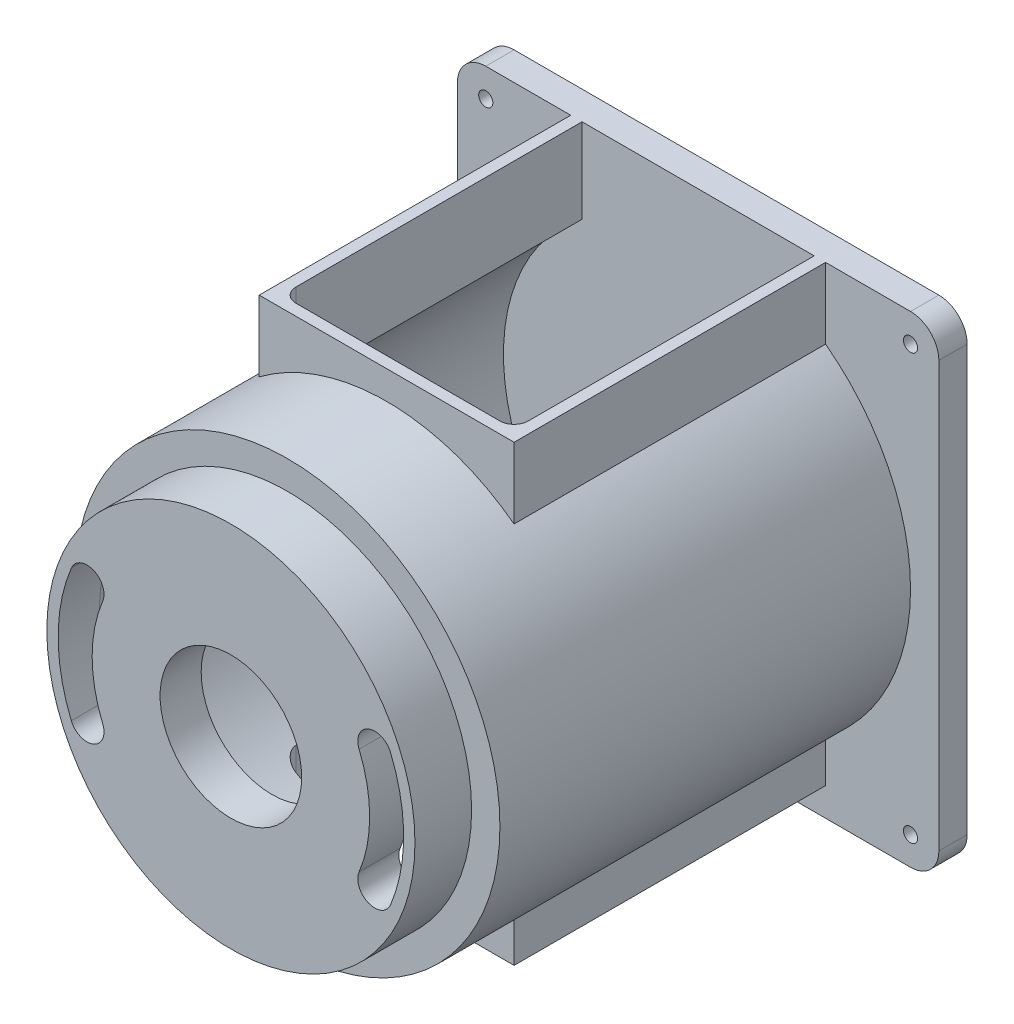
SolidWorks part; units mm, degrees
material "Cast Stainless Steel"
ref_plane "Front Plane" through (0, 0, 0) normal (0, 0, 1) x (1, 0, 0)
ref_plane "Top Plane" through (0, 0, 0) normal (0, 1, 0) x (1, 0, 0)
ref_plane "Right Plane" through (0, 0, 0) normal (1, 0, 0) x (0, 0, -1)
other "Center of Mass"
sketch "Sketch1" plane through (0, 0, 0) normal (0, 1, 0) x (1, 0, 0)
  line L1 (150, -170) -> (-150, -170)
  line L2 (170, -150) -> (170, 150)
  line L3 (150, 170) -> (-150, 170)
  line L4 (-170, -150) -> (-170, 150)
  line L5 (170, -170) -> (-170, 170) construction
  line L6 (170, 170) -> (-170, -170) construction
  arc A0 (170, -150) -> (150, -170) centre (150, -150) cw
  arc A1 (-170, -150) -> (-150, -170) centre (-150, -150) ccw
  arc A2 (150, 170) -> (170, 150) centre (150, 150) cw
  arc A3 (-150, 170) -> (-170, 150) centre (-150, 150) ccw
  point P0 (0, 0)
  dimension "D3" = 20
  dimension "D1" = 340
  dimension "D2" = 340
extrude "Boss-Extrude1" add sketch "Sketch1" along normal blind 20
sketch "Sketch2" plane through (0, 20, 0) normal (0, 1, 0) x (1, 0, 0)
  line L4 (170, -150) -> (170, 150)
  line L5 (150, 170) -> (-150, 170)
  line L6 (-170, 150) -> (-170, -150)
  line L7 (-150, -170) -> (150, -170)
  line L8 (170, -150) -> (170, 150)
  line L9 (150, 170) -> (-150, 170)
  line L10 (-170, 150) -> (-170, -150)
  line L11 (-150, -170) -> (150, -170)
  line L12 (-150, 0) -> (-150, -90)
  line L13 (-150, -90) -> (-120, -90)
  line L14 (120, -90) -> (150, -90)
  line L15 (0, 0) -> (-150, 0) construction
  line L16 (150, -150) -> (150, 150)
  line L17 (150, 150) -> (-150, 150)
  line L18 (-150, 150) -> (-150, -150)
  line L19 (-150, -150) -> (150, -150)
  line L20 (150, -150) -> (150, 150)
  line L21 (150, 150) -> (-150, 150)
  line L22 (-150, 150) -> (-150, -150)
  line L23 (-150, -150) -> (150, -150)
  line L24 (150, -90) -> (170, -90)
  line L25 (150, 90) -> (170, 90)
  line L26 (120, 90) -> (150, 90)
  line L27 (-150, 90) -> (-120, 90)
  arc A4 (150, -170) -> (170, -150) centre (150, -150) ccw
  arc A5 (170, 150) -> (150, 170) centre (150, 150) ccw
  arc A6 (-150, 170) -> (-170, 150) centre (-150, 150) ccw
  arc A7 (-170, -150) -> (-150, -170) centre (-150, -150) ccw
  arc A8 (150, -170) -> (170, -150) centre (150, -150) ccw
  arc A9 (170, 150) -> (150, 170) centre (150, 150) ccw
  arc A10 (-150, 170) -> (-170, 150) centre (-150, 150) ccw
  arc A11 (-170, -150) -> (-150, -170) centre (-150, -150) ccw
  circle A12 centre (0, 0) radius 150
  dimension "D3" = 30
  dimension "D1" = 0
  dimension "D2" = 20
extrude "Boss-Extrude2" add sketch "Sketch2" along normal blind 220 contours A12 | A12 L12 L13 | A12 L14 L20 | L25 L20 L24 L8 | A12 L20 L26 | A12 L27 L22 region at (160, 20, 0) region at (141.1785, 20, 67.9748) region at (141.1785, 20, -67.9748) region at (0, 20, 0) region at (-141.1785, 20, 67.9748) region at (-141.1785, 20, -67.9748)
sketch "Sketch3" plane through (0, 240, 0) normal (0, 1, 0) x (1, 0, 0)
  line L6 (170, -90) -> (170, 90)
  line L7 (170, 90) -> (120, 90)
  line L8 (-120, 90) -> (-150, 90)
  line L9 (-150, 90) -> (-150, -90)
  line L10 (-150, -90) -> (-120, -90)
  line L11 (120, -90) -> (170, -90)
  line L12 (170, -90) -> (170, 90)
  line L13 (170, 90) -> (120, 90)
  line L14 (-120, 90) -> (-150, 90)
  line L15 (-150, 90) -> (-150, -90)
  line L16 (-150, -90) -> (-120, -90)
  line L17 (120, -90) -> (170, -90)
  circle A0 centre (0, 0) radius 150
  arc A2 (120, 90) -> (-120, 90) centre (0, 0) ccw
  arc A3 (-120, -90) -> (120, -90) centre (0, 0) ccw
  arc A4 (120, 90) -> (-120, 90) centre (0, 0) ccw
  arc A5 (-120, -90) -> (120, -90) centre (0, 0) ccw
  arc M11 (120, 90) -> (-120, 90) centre (0, 0) ccw
  arc M15 (-120, -90) -> (120, -90) centre (0, 0) ccw
  dimension "D1" = 0
extrude "Boss-Extrude3" add sketch "Sketch3" along normal blind 70 contours A0 M15 M11 region at (0, 240, 0)
sketch "Sketch4" plane through (0, 310, 0) normal (0, 1, 0) x (1, 0, 0)
  circle A1 centre (0, 0) radius 150
  circle A2 centre (0, 0) radius 150
  circle A4 centre (0, 0) radius 130
  circle A5 centre (0, 0) radius 130
  dimension "D1" = 0
  dimension "D2" = 20
extrude "Boss-Extrude4" add sketch "Sketch4" along normal blind 40 contours A5 region at (0, 310, 0)
sketch "Sketch18" plane through (0, 20, 0) normal (0, 1, 0) x (1, 0, 0)
  circle A0 centre (0, 0) radius 137.5
  dimension "D1" = 275
extrude "Cut-Extrude6" cut sketch "Sketch18" along normal blind 256
ref_point "Point1"
move or copy body "Body-Move/Copy1" bodies to move or copy 115 copy no rotation origin (0, 0, 0) rotation axis (1, 0, 0) rotation angle 90
move or copy body "Body-Move/Copy2" bodies to move or copy 118 copy no rotation origin (0, 0, 0) rotation axis (0, 0, -1) rotation angle 90
move or copy body "Body-Move/Copy3" bodies to move or copy 119 copy no rotation origin (0, 0, 0) rotation axis (0, 0, 1) rotation angle 180
sketch "Sketch19" plane through (0, 0, 350) normal (0, 0, 1) x (1, 0, 0)
  circle A0 centre (0, 0) radius 50
  dimension "D1" = 100
extrude "Cut-Extrude7" cut sketch "Sketch19" against normal up to surface (74 mm away) up to face at (137.5, 0, 276)
sketch "Sketch20" plane through (0, 0, 0) normal (0, 0, -1) x (-1, 0, 0)
  line L1 (-150, 150) -> (150, 150)
  line L2 (-150, 150) -> (-150, -150)
  line L3 (-150, -150) -> (150, -150)
  line L4 (150, 150) -> (150, -150)
  line L5 (-150, 150) -> (150, -150) construction
  line L6 (-150, -150) -> (150, 150) construction
  circle A0 centre (150, -150) radius 5
  circle A1 centre (-150, -150) radius 5
  circle A2 centre (-150, 150) radius 5
  circle A3 centre (150, 150) radius 5
  point P0 (0, 0)
  point P7 (150, -150)
  point P8 (-150, -150)
  point P9 (150, 150)
  point P10 (-150, 150)
  dimension "D3" = 10
  dimension "D4" = 10
  dimension "D5" = 10
  dimension "D6" = 10
  dimension "D1" = 300
  dimension "D2" = 300
extrude "Cut-Extrude8" cut sketch "Sketch20" against normal up to surface (20 mm away) contours L3 A0 L4 | L4 A0 L3 | L2 A1 L3 | L3 A1 L2 | L1 A2 L2 | L2 A2 L1 | L4 A3 L1 | L1 A3 L4 region at (150.7074, 150.7074, 0) region at (147.8779, 147.8779, 0) region at (-150.7074, 150.7074, 0) region at (-147.8779, 147.8779, 0) region at (147.8779, -147.8779, 0) region at (150.7074, -150.7074, 0) region at (-150.7074, -150.7074, 0) region at (-147.8779, -147.8779, 0) up to face at (0, 2.5, 20)
sketch "Sketch26" plane through (0, 0, 350) normal (0, 0, 1) x (1, 0, 0)
  line L0 (0, 0) -> (0, 110) construction
  line L1 (0, 0) -> (42.0952, 101.6267) construction
  line L2 (0, 0) -> (101.6267, -42.0952) construction
  line L3 (0, 0) -> (110, 0) construction
  line L4 (0, 0) -> (101.6267, 42.0952) construction
  circle A0 centre (0, 0) radius 110
  circle A1 centre (0, 0) radius 130
  circle A2 centre (0, 0) radius 130
  circle A3 centre (101.6267, -42.0952) radius 12
  circle A4 centre (110, 0) radius 12
  circle A5 centre (0, 0) radius 98
  circle A6 centre (0, 0) radius 122
  circle A7 centre (101.6267, 42.0952) radius 12
  dimension "D2" = 220
  dimension "D4" = 24
  dimension "D5" = 24
  dimension "D8" = 196
  dimension "D9" = 244
  dimension "D10" = 24
  dimension "D3" = 22.5
  dimension "D6" = 22.5
  dimension "D7" = 22.5
  dimension "D1" = 0
extrude "Cut-Extrude11" cut sketch "Sketch26" against normal up to surface (74 mm away) contours A0 A3 | A0 A3 | A3 A6 A4 A0 | A5 A3 A0 A4 | A0 A4 | A7 A5 A4 A0 | A7 A0 A4 A6 | A7 A0 | A0 A7 | A0 A4 region at (104.791, 0, 350) region at (114.9732, 0, 350) region at (101.2141, 20.1327, 350) region at (114.2829, 22.7323, 350) region at (114.2829, -22.7323, 350) region at (101.2141, -20.1327, 350) region at (96.8142, 40.1018, 350) region at (106.2214, 43.9984, 350) region at (106.2214, -43.9984, 350) region at (96.8142, -40.1018, 350) up to face at (50, 0, 276)
sketch "Sketch29" plane through (0, 0, 276) normal (0, 0, -1) x (-1, 0, 0)
  circle A0 centre (0, 0) radius 122.5
  circle A1 centre (0, 0) radius 137.5
  circle A2 centre (0, 0) radius 137.5
  arc M2 (-90.5402, -37.503) -> (-112.7133, -46.6874) centre (-101.6267, -42.0952) cw
  arc M3 (-112.7133, -46.6874) -> (-112.7133, 46.6874) centre (0, 0) cw
  arc M4 (-112.7133, 46.6874) -> (-90.5402, 37.503) centre (-101.6267, 42.0952) cw
  arc M5 (-90.5402, 37.503) -> (-90.5402, -37.503) centre (0, 0) ccw
  circle M6 centre (0, 0) radius 50
  dimension "D1" = 0
  dimension "D2" = 15
extrude "Cut-Extrude12" cut sketch "Sketch29" against normal blind 45 contours A0 M5 M2 M3 M4 M6 region at (122.1535, 0, 276)
mirror "Mirror1" about plane through (0, 0, 0) normal (1, 0, 0) of "Cut-Extrude11"
sketch "Sketch33" plane through (0, -150, 0) normal (0, -1, 0) x (1, 0, 0)
  line L5 (-90, 20) -> (90, 20)
  line L6 (90, 20) -> (90, 240)
  line L7 (90, 240) -> (0, 240)
  line L8 (0, 240) -> (-90, 240)
  line L9 (-90, 240) -> (-90, 20)
  line L10 (-90, 20) -> (90, 20)
  line L11 (90, 20) -> (90, 240)
  line L12 (90, 240) -> (0, 240)
  line L13 (0, 240) -> (-90, 240)
  line L14 (-90, 240) -> (-90, 20)
  line L15 (-82, 28) -> (-82, 20)
  line L16 (82, 28) -> (82, 20)
  line L20 (-82, 28) -> (82, 28)
  line L21 (82, 28) -> (82, 232)
  line L22 (82, 232) -> (0, 232)
  line L23 (0, 232) -> (-82, 232)
  line L24 (-82, 232) -> (-82, 28)
  line L26 (82, 28) -> (82, 222)
  line L27 (72, 232) -> (0, 232)
  line L28 (0, 232) -> (-72, 232)
  line L29 (-82, 222) -> (-82, 28)
  arc A0 (82, 222) -> (72, 232) centre (72, 222) ccw
  arc A1 (-82, 222) -> (-72, 232) centre (-72, 222) cw
  dimension "D3" = 10
  dimension "D1" = 0
  dimension "D2" = 8
extrude "Cut-Extrude13" cut sketch "Sketch33" against normal up to surface (320 mm away) contours A1 L29 L15 L10 L16 L26 A0 L27 L28 region at (0, -150, 24) region at (0, -150, 129.8718) up to face at (170, 0, 10)
